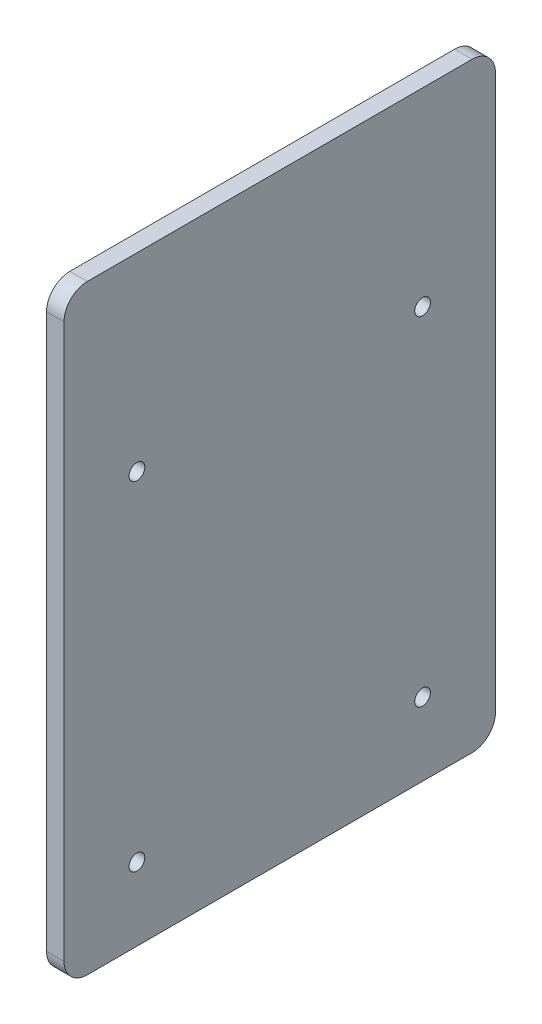
SolidWorks part; units mm, degrees
ref_plane "Front Plane" through (0, 0, 0) normal (1, 0, 0) x (0, 1, 0)
ref_plane "Top Plane" through (0, 0, 0) normal (0, 0, 1) x (0, 1, 0)
ref_plane "Right Plane" through (0, 0, 0) normal (0, 1, 0) x (-1, 0, 0)
sketch "Sketch1" plane through (0, 0, 0) normal (1, 0, 0) x (0, 1, 0)
  line L0 (-29, 0) -> (29, 0) construction
  line L1 (29, 24.5) -> (-29, 24.5) construction
  line L2 (29, 24.5) -> (29, -24.5) construction
  line L3 (29, -24.5) -> (-29, -24.5) construction
  line L4 (-29, 24.5) -> (-29, -24.5) construction
  line L5 (29, 24.5) -> (-29, -24.5) construction
  line L6 (29, -24.5) -> (-29, 24.5) construction
  line L7 (0, 24.5) -> (0, -24.5) construction
  line L8 (57.5, 33) -> (61.5, 33)
  line L9 (-32.5, 28) -> (52.5, 28)
  line L10 (-32.5, 28) -> (-32.5, -28)
  line L11 (-32.5, -28) -> (52.5, -28)
  line L12 (52.5, 28) -> (52.5, -28)
  line L13 (57.5, 33) -> (-37.5, 33)
  line L14 (57.5, 33) -> (57.5, -33) construction
  line L15 (57.5, -33) -> (-37.5, -33)
  line L16 (-37.5, 33) -> (-37.5, -33)
  line L17 (61.5, 37) -> (-41.5, 37)
  line L18 (61.5, 37) -> (61.5, -37)
  line L19 (61.5, -37) -> (-41.5, -37)
  line L20 (-41.5, 37) -> (-41.5, -37)
  line L21 (57.5, -33) -> (61.5, -33)
  line L22 (-29, -24.5) -> (-29, -37)
  line L23 (29, -24.5) -> (29, -37)
  circle A0 centre (-29, 24.5) radius 1.35
  circle A1 centre (-29, -24.5) radius 1.35
  circle A2 centre (29, -24.5) radius 1.35
  circle A3 centre (29, 24.5) radius 1.35
  circle A4 centre (-29, 24.5) radius 3.25
  circle A5 centre (-29, -24.5) radius 3.25
  circle A6 centre (29, -24.5) radius 3.25
  circle A7 centre (29, 24.5) radius 3.25
  point P0 (0, 0)
  dimension "D3" = 2.7
  dimension "D8" = 6.5
  dimension "D1" = 58
  dimension "D2" = 49
  dimension "D4" = 85
  dimension "D5" = 56
  dimension "D6" = 3.5
  dimension "D7" = 3.5
  dimension "D9" = 5
  dimension "D10" = 5
  dimension "D11" = 5
  dimension "D12" = 5
  dimension "D13" = 4
  dimension "D14" = 4
  dimension "D15" = 4
  dimension "D16" = 4
extrude "Boss-Extrude2" add sketch "Sketch1" against normal blind 3 contours L20 L19 L18 L17
extrude "Cut-Extrude1" cut sketch "Sketch1<12>" against normal blind 3 contours A1 | A0 | A3 | A2 region at (0, -29.9276, -23.5724)
sketch "Sketch1<12>" plane through (0, 0, 0) normal (1, 0, 0) x (0, 1, 0) same geometry as "Sketch1"
fillet "Fillet1" radius 4 4 edges at (-1.5, -41.5, 37) (-1.5, 61.5, 37) (-1.5, 61.5, -37) (-1.5, -41.5, -37)
